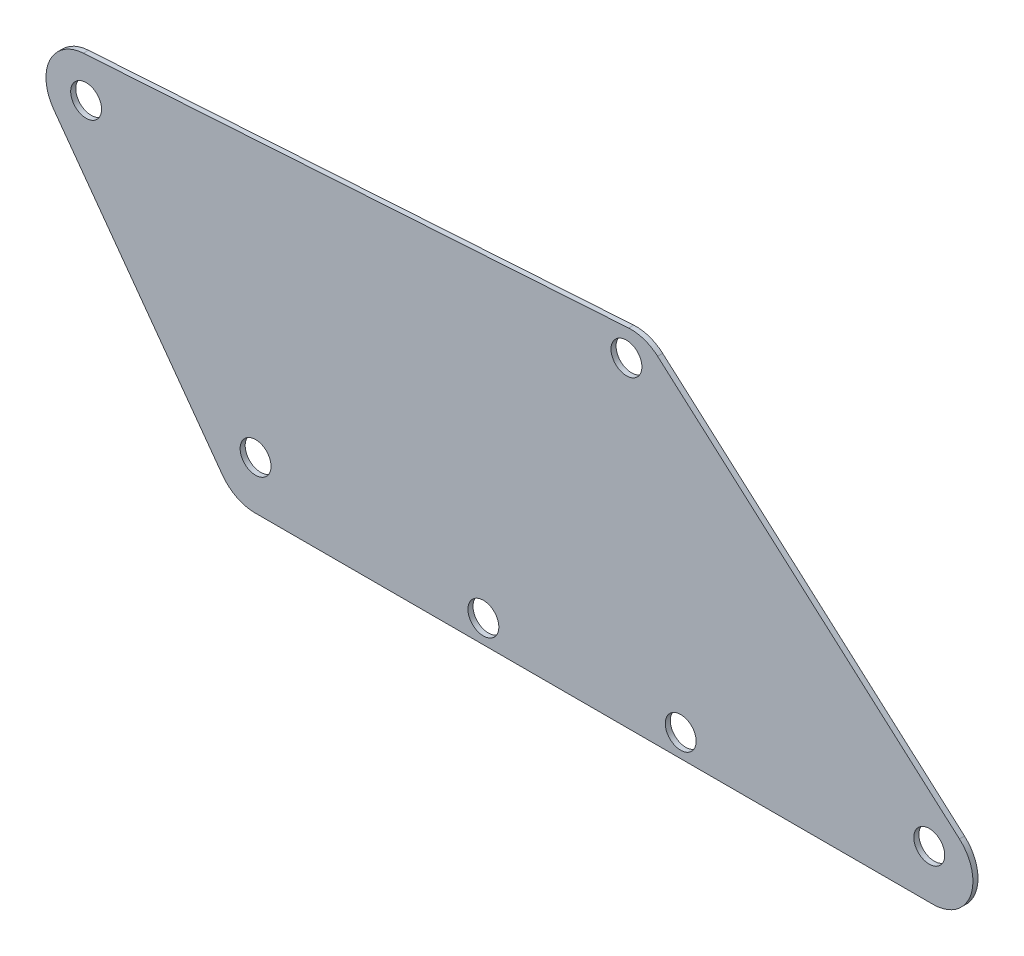
SolidWorks part; units mm, degrees
ref_plane "Front Plane" through (0, 0, 0) normal (0, 0, 1) x (1, 0, 0)
ref_plane "Top Plane" through (0, 0, 0) normal (0, 1, 0) x (1, 0, 0)
ref_plane "Right Plane" through (0, 0, 0) normal (1, 0, 0) x (0, 0, -1)
sketch "Sketch3" plane through (0, 0, 0) normal (0, 0, 1) x (1, 0, 0)
  line L0 (-105.0544, 1.9987) -> (28.8099, 1.9987)
  line L3 (-144.7818, 51.1553) -> (-111.4337, 5.2494)
  line L4 (-130.8953, -6.016) -> (39.056, -6.016)
  line L7 (-138.9015, 63.6585) -> (-31.2776, 70.4842)
  line L8 (-25.5532, 68.52) -> (34.0353, 15.7884)
  arc A0 (28.8099, 1.9987) -> (34.0353, 15.7884) centre (28.8099, 9.8836) ccw
  arc A1 (-25.5532, 68.52) -> (-31.2776, 70.4842) centre (-30.7786, 62.6152) ccw
  arc A2 (-105.0544, 1.9987) -> (-111.4337, 5.2494) centre (-105.0544, 9.8836) cw
  arc A3 (-144.7818, 51.1553) -> (-138.9015, 63.6585) centre (-138.4025, 55.7894) cw
  circle A11 centre (49.307, 58.8735) radius 21
  circle A13 centre (-59.9429, 6.5523) radius 3.05
  circle A14 centre (-104.9148, 11.5444) radius 3.05
  circle A15 centre (-20.9941, 6.4971) radius 3.05
  circle A16 centre (28.0724, 11.5486) radius 3.05
  circle A17 centre (-31.7004, 65.1519) radius 3.05
  circle A18 centre (-138.3619, 55.8478) radius 3.05
  point P3 (0, 0)
  dimension "D1" = 7.8849
extrude "Boss-Extrude2" add sketch "Sketch3" along normal blind 1 contours A3 L3 A2 L0 A0 L8 A1 L7 A18 A17 A16 A15 A14 A13 region at (-58.2224, 33.7177, 0)
